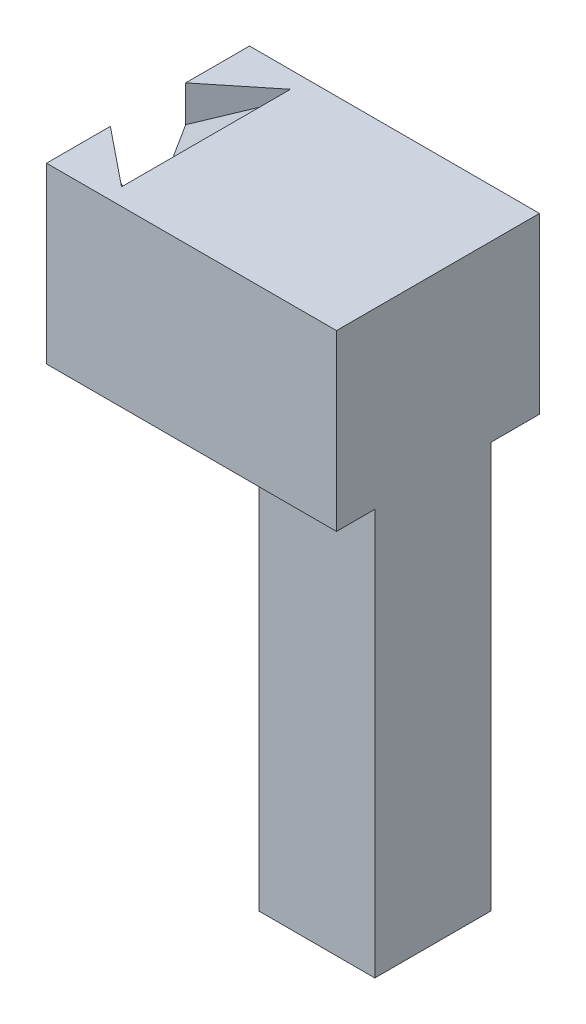
SolidWorks part; units mm, degrees
ref_plane "Front Plane" through (0, 0, 0) normal (0, 0, 1) x (1, 0, 0)
ref_plane "Top Plane" through (0, 0, 0) normal (0, 1, 0) x (1, 0, 0)
ref_plane "Right Plane" through (0, 0, 0) normal (1, 0, 0) x (0, 0, -1)
sketch "Sketch1" plane through (0, 0, 0) normal (0, 1, 0) x (1, 0, 0)
  line L1 (-20, -20) -> (20, -20)
  line L2 (-20, -20) -> (-20, 20)
  line L3 (-20, 20) -> (20, 20)
  line L4 (20, -20) -> (20, 20)
  line L5 (-20, -20) -> (20, 20) construction
  line L6 (-20, 20) -> (20, -20) construction
  point P0 (0, 0)
  dimension "D1" = 40
sketch3d "3DSketch1"
  line L0 (0, 0, 0) -> (0, 200, 0) construction
  line L3 (0, 200, 0) -> (0, 0, 0)
  dimension "D1" = 200
sweep "Sweep1" add profiles "Sketch1" path "3DSketch1"
sketch "Sketch2" plane through (-20, 0, 0) normal (-1, 0, 0) x (0, 0, 1)
  line L0 (-20, 200) -> (20, 200) construction
  line L1 (-36.772, 140) -> (33.228, 140)
  line L2 (-36.772, 140) -> (-36.772, 200)
  line L3 (-36.772, 200) -> (33.228, 200)
  line L4 (33.228, 140) -> (33.228, 200)
  line L5 (-36.772, 140) -> (33.228, 200) construction
  line L6 (-36.772, 200) -> (33.228, 140) construction
  point P0 (-1.772, 170)
  point P5 (0, 172.6984)
  point P6 (-1.772, 163.3263)
  dimension "D1" = 30
  dimension "D2" = 60
  dimension "D3" = 70
extrude "Boss-Extrude1" add sketch "Sketch2" along normal blind 60 and the other way up to surface (40 mm away) other way up to face at (20, 100, 0)
sketch "Sketch3" plane through (-80, 0, 0) normal (-1, 0, 0) x (0, 0, 1)
  line L0 (33.228, 200) -> (-36.772, 200) construction
  line L1 (-1.772, 165) -> (11.2184, 187.5)
  line L2 (11.2184, 187.5) -> (-14.7624, 187.5)
  line L3 (-14.7624, 187.5) -> (-1.772, 165)
  line L4 (33.228, 140) -> (33.228, 200) construction
  circle A0 centre (-1.772, 180) radius 7.5 construction
  point P1 (0, 0)
  point P10 (11.044, 177.2018)
  dimension "D3" = 15
  dimension "D1" = 20
  dimension "D2" = 35
extrude "Cut-Extrude1" cut sketch "Sketch3" against normal blind 20 draft 25 draft outward yes
sketch "Sketch5" plane through (0, 200, 0) normal (0, 1, 0) x (1, 0, 0)
  line L0 (-80, 14.7624) -> (-60, 30.9158)
  line L1 (-60, 30.9158) -> (-60, -27.3717)
  line L2 (-60, -27.3717) -> (-80, -11.2184)
  line L3 (-80, -11.2184) -> (-80, 14.7624)
extrude "Cut-Extrude4" cut sketch "Sketch5" against normal up to surface (12.5 mm away) up to face at (-70, 192.1631, -1.772)
